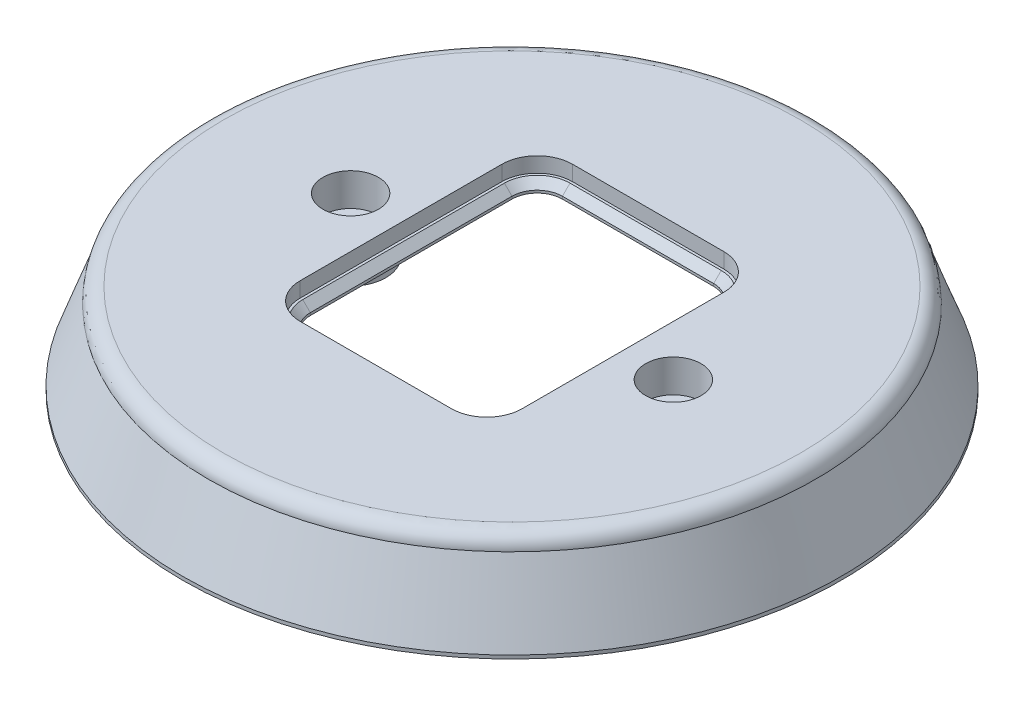
SolidWorks part; units mm, degrees
ref_plane "Alzado" through (0, 0, 0) normal (0, 0, 1) x (1, 0, 0)
ref_plane "Planta" through (0, 0, 0) normal (0, 1, 0) x (1, 0, 0)
ref_plane "Vista lateral" through (0, 0, 0) normal (1, 0, 0) x (0, 0, -1)
sketch "Croquis1" plane through (0, 0, 0) normal (0, 0, 1) x (1, 0, 0)
  line L1 (-65.3603, 76.9046) -> (-65.3603, 76.2206)
  line L3 (-65.3603, 76.2206) -> (-63.4809, 76.2206)
  line L4 (60.4813, 83) -> (-60.4813, 83) construction
  line L5 (-60.4813, 83) -> (-71.9464, 51.5) construction
  line L6 (0, 89) -> (-58.8296, 89)
  line L7 (-58.8296, 89) -> (-63.4809, 76.2206)
  line L8 (0, 91) -> (-60.23, 91)
  line L9 (-60.23, 91) -> (-65.3603, 76.9046)
  line L10 (-65.3603, 76.9046) -> (-63.4809, 76.2206) construction
  line L11 (0, 89) -> (0, 91)
  line L13 (58.8333, 91) -> (-60.23, 91) construction
  line L14 (58.8333, 89) -> (-58.8296, 89) construction
  line L15 (-60.23, 91) -> (-64.5175, 79.2201) construction
  line L16 (-58.8296, 89) -> (-62.6381, 78.5361) construction
  dimension "D2" = 2
  dimension "D3" = 15
  dimension "D1" = 6
  dimension "D4" = 0.5
revolve "Revolución1" add sketch "Croquis1" angle 360 about L11
sketch "Croquis2" plane through (0, 91, 0) normal (0, 1, 0) x (1, 0, 0)
  circle A1 centre (32, 0) radius 3.5
  circle A2 centre (32, 0) radius 3.5
  circle A3 centre (-32, 0) radius 3.5
  circle A4 centre (-32, 0) radius 3.5
  dimension "D1" = 0
  dimension "D2" = 0
extrude "Cortar-Extruir1" cut sketch "Croquis2" against normal up to next
sketch "Croquis3" plane through (0, 89, 0) normal (0, -1, 0) x (1, 0, 0)
  circle A0 centre (32, 0) radius 3.5 construction
  circle A1 centre (-32, 0) radius 3.5 construction
  circle A2 centre (32, 0) radius 3.5
  circle A3 centre (-32, 0) radius 3.5
  circle A4 centre (-32, 0) radius 7
  circle A5 centre (32, 0) radius 7
  dimension "D1" = 3.5
  dimension "D2" = 3.5
extrude "Saliente-Extruir1" add sketch "Croquis3" along normal blind 6
sketch "Croquis4" plane through (0, 91, 0) normal (0, 1, 0) x (1, 0, 0)
  circle A0 centre (0, 0) radius 60.23 construction
  circle A1 centre (0, 0) radius 60.23
  circle A2 centre (32, 0) radius 3.5 construction
  circle A3 centre (-32, 0) radius 3.5 construction
  circle A4 centre (32, 0) radius 3.5
  circle A5 centre (-32, 0) radius 3.5
extrude "Saliente-Extruir2" add sketch "Croquis4" along normal blind 3
sketch "Croquis5" plane through (0, 94, 0) normal (0, 1, 0) x (1, 0, 0)
  circle A0 centre (-32, 0) radius 5.5
  circle A1 centre (32, 0) radius 5.5
  dimension "D1" = 11
extrude "Cortar-Extruir2" cut sketch "Croquis5" against normal blind 6.5
sketch "Croquis6" plane through (0, 94, 0) normal (0, 1, 0) x (1, 0, 0)
  line L1 (-15, -25) -> (15, -25)
  line L2 (-20, -20) -> (-20, 20)
  line L3 (-15, 25) -> (15, 25)
  line L4 (20, -20) -> (20, 20)
  line L5 (-20, -25) -> (20, 25) construction
  line L6 (-20, 25) -> (20, -25) construction
  arc A0 (-15, -25) -> (-20, -20) centre (-15, -20) cw
  arc A1 (15, -25) -> (20, -20) centre (15, -20) ccw
  arc A2 (15, 25) -> (20, 20) centre (15, 20) cw
  arc A3 (-20, 20) -> (-15, 25) centre (-15, 20) cw
  point P0 (0, 0)
  point P6 (-20, 0)
  point P7 (20, 0)
  point P8 (0, 25)
  point P9 (0, -25)
  dimension "D3" = 5
  dimension "D1" = 40
  dimension "D2" = 50
extrude "Cortar-Extruir3" cut sketch "Croquis6" against normal up to next
sketch "Croquis7" plane through (0, 94, 0) normal (0, 1, 0) x (1, 0, 0)
  line L0 (-15, -25) -> (15, -25) construction
  line L1 (20, -20) -> (20, 20) construction
  line L2 (15, 25) -> (-15, 25) construction
  line L3 (-20, 20) -> (-20, -20) construction
  line L4 (-15, -25) -> (15, -25)
  line L5 (20, -20) -> (20, 20)
  line L6 (15, 25) -> (-15, 25)
  line L7 (-20, 20) -> (-20, -20)
  line L8 (-15, -27) -> (15, -27)
  line L9 (22, -20) -> (22, 20)
  line L10 (15, 27) -> (-15, 27)
  line L11 (-22, 20) -> (-22, -20)
  arc A0 (-20, -20) -> (-15, -25) centre (-15, -20) ccw construction
  arc A1 (15, -25) -> (20, -20) centre (15, -20) ccw construction
  arc A2 (20, 20) -> (15, 25) centre (15, 20) ccw construction
  arc A3 (-15, 25) -> (-20, 20) centre (-15, 20) ccw construction
  arc A4 (-20, -20) -> (-15, -25) centre (-15, -20) ccw
  arc A5 (15, -25) -> (20, -20) centre (15, -20) ccw
  arc A6 (20, 20) -> (15, 25) centre (15, 20) ccw
  arc A7 (-15, 25) -> (-20, 20) centre (-15, 20) ccw
  arc A9 (15, -27) -> (22, -20) centre (15, -20) ccw
  circle A10 centre (0, 0) radius 57.23
  circle A11 centre (0, 0) radius 57.23
  arc A12 (22, 20) -> (15, 27) centre (15, 20) ccw
  arc A13 (-15, 27) -> (-22, 20) centre (-15, 20) ccw
  arc A14 (-22, -20) -> (-15, -27) centre (-15, -20) ccw
  dimension "D1" = 3
  dimension "D2" = 2
extrude "Cortar-Extruir4" cut sketch "Croquis7" against normal blind 3 contours L8 A9 L9 A12 L10 A13 L11 A14
chamfer "Chaflán1" distance 1.5 angle 45 8 edges at (0, 91, 25) (-18.5355, 91, 23.5355) (18.5355, 91, 23.5355) (-20, 91, 0) (20, 91, 0) (-18.5355, 91, -23.5355) (18.5355, 91, -23.5355) (0, 91, -25)
fillet "Redondeo1" radius 3 1 edges at (0, 94, 60.23)
